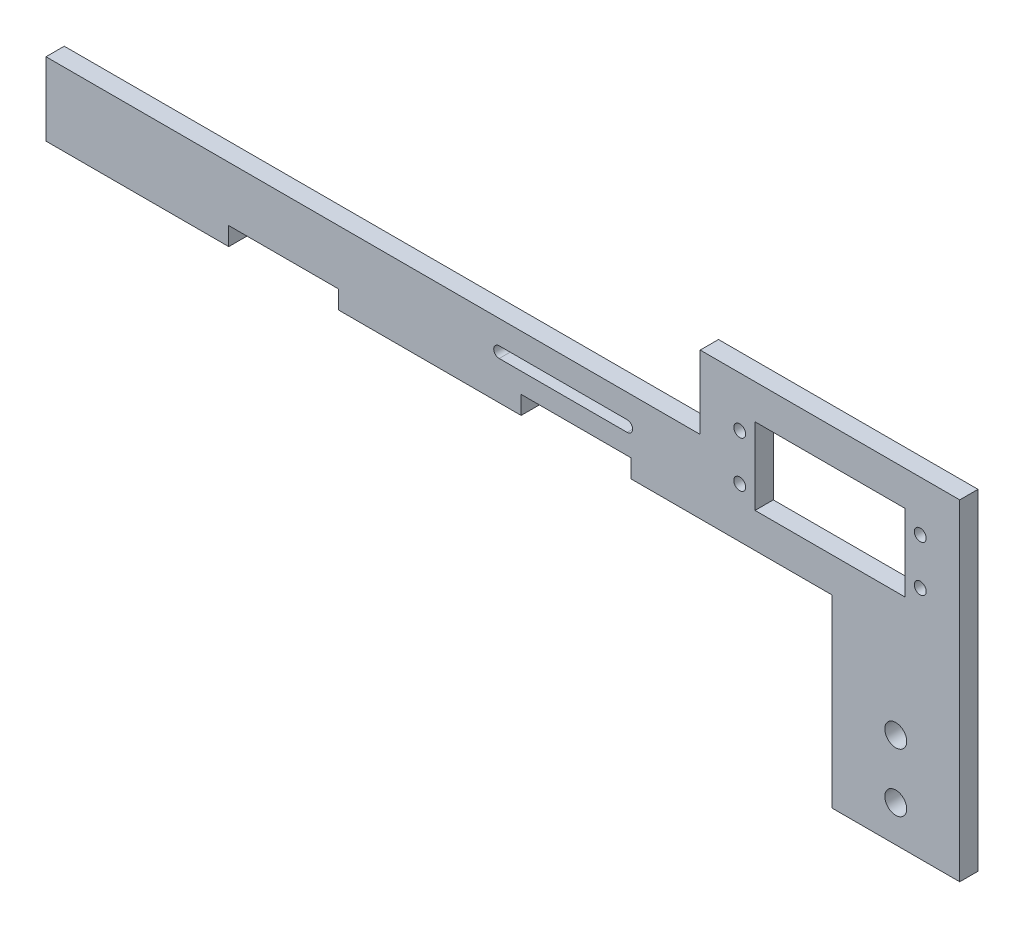
SolidWorks part; units mm, degrees
ref_plane "Plano frontal" through (0, 0, 0) normal (0, 0, 1) x (1, 0, 0)
ref_plane "Plano superior" through (0, 0, 0) normal (0, 1, 0) x (1, 0, 0)
ref_plane "Plano direito" through (0, 0, 0) normal (1, 0, 0) x (0, 0, -1)
sketch "Esboço1" plane through (0, 0, 0) normal (0, 0, 1) x (1, 0, 0)
  line L0 (194, 0) -> (235, 0) construction
  line L1 (215, -20) -> (160, -20)
  line L2 (250, -20) -> (250, 20)
  line L3 (250, 20) -> (179, 20)
  line L4 (0, -20) -> (0, 0)
  line L5 (194, 10.5) -> (235, 10.5)
  line L6 (194, 10.5) -> (194, -10.5)
  line L7 (194, -10.5) -> (235, -10.5)
  line L8 (235, 10.5) -> (235, -10.5)
  line L9 (214.5, 10.5) -> (214.5, -10.5) construction
  line L10 (0, 0) -> (179, 0)
  line L11 (179, 0) -> (179, 20)
  line L12 (250, 0) -> (184.4373, 0) construction
  line L13 (50, -20) -> (50, -15)
  line L14 (50, -15) -> (80, -15)
  line L15 (80, -15) -> (80, -20)
  line L16 (130, -20) -> (130, -15)
  line L17 (130, -15) -> (160, -15)
  line L18 (160, -15) -> (160, -20)
  line L19 (50, -20) -> (0, -20)
  line L20 (130, -20) -> (80, -20)
  line L21 (124, -8) -> (159, -8) construction
  line L22 (124, -6.5) -> (159, -6.5)
  line L23 (124, -9.5) -> (159, -9.5)
  line L26 (215, -20) -> (215, -70.5)
  line L27 (215, -70.5) -> (250, -70.5)
  line L28 (250, -20) -> (250, -70.5)
  circle A0 centre (189.8, 6.3) radius 1.625
  circle A1 centre (239.2, 6.3) radius 1.625
  circle A2 centre (239.2, -6.3) radius 1.625
  circle A3 centre (189.8, -6.3) radius 1.625
  arc A5 (124, -6.5) -> (124, -9.5) centre (124, -8) ccw
  arc A6 (159, -9.5) -> (159, -6.5) centre (159, -8) ccw
  circle A7 centre (232.5, -60.5) radius 3
  circle A8 centre (232.5, -44.5) radius 3
  point P36 (141.5, -8)
  dimension "D8" = 3.25
  dimension "D9" = 4.2
  dimension "D19" = 1.5
  dimension "D27" = 6
  dimension "D29" = 10
  dimension "D30" = 6
  dimension "D3" = 41
  dimension "D4" = 15
  dimension "D5" = 21
  dimension "D6" = 9.5
  dimension "D7" = 4.2
  dimension "D10" = 20
  dimension "D11" = 15
  dimension "D12" = 179
  dimension "D13" = 50
  dimension "D14" = 30
  dimension "D15" = 5
  dimension "D16" = 50
  dimension "D17" = 30
  dimension "D18" = 5
  dimension "D20" = 8
  dimension "D21" = 35
  dimension "D22" = 20
  dimension "D23" = 71
  dimension "D24" = 40
  dimension "D25" = 9.5
  dimension "D26" = 35
  dimension "D28" = 50.5
  dimension "D31" = 16
extrude "Ressalto-extrusão1" add sketch "Esboço1" along normal blind 5 contours L20 L16 L17 L18 L1 L2 L3 L11 L10 L4 L19 L13 L14 L15 A1 A0 L5 L8 L7 L6 A2 A3 region at (187.5, -17.3412, 0)
